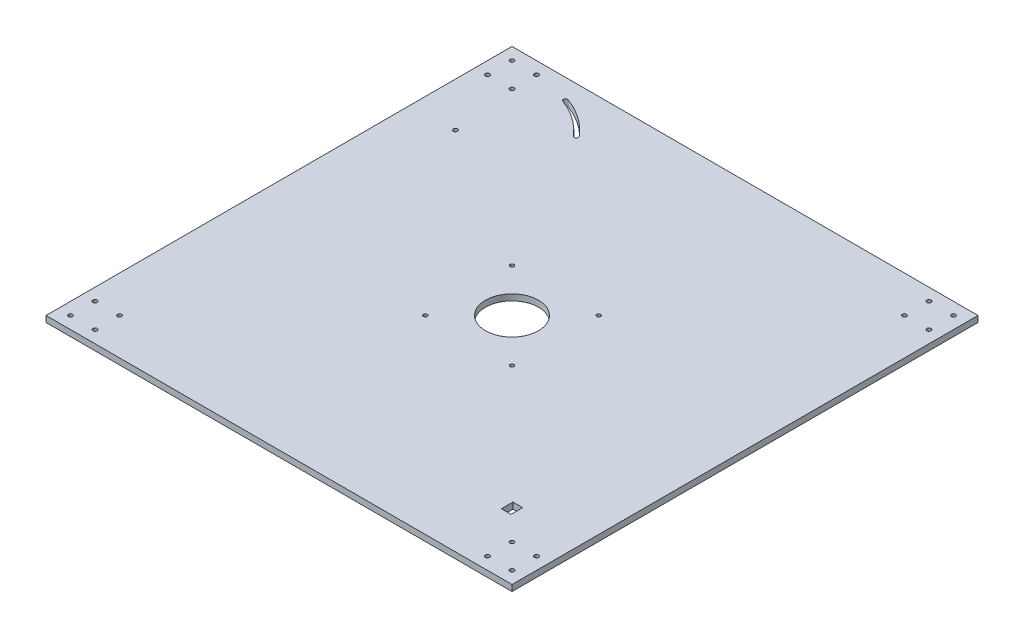
SolidWorks part; units mm, degrees
ref_plane "Front Plane" through (0, 0, 0) normal (0, 0, 1) x (1, 0, 0)
ref_plane "Top Plane" through (0, 0, 0) normal (0, 1, 0) x (1, 0, 0)
ref_plane "Right Plane" through (0, 0, 0) normal (1, 0, 0) x (0, 0, -1)
sketch "Sketch1" plane through (0, 0, 0) normal (0, 1, 0) x (1, 0, 0)
  line L1 (-241.3, -241.3) -> (241.3, -241.3)
  line L2 (-241.3, -241.3) -> (-241.3, 241.3)
  line L3 (-241.3, 241.3) -> (241.3, 241.3)
  line L4 (241.3, -241.3) -> (241.3, 241.3)
  line L5 (-241.3, -241.3) -> (241.3, 241.3) construction
  line L6 (-241.3, 241.3) -> (241.3, -241.3) construction
  point P0 (0, 0)
  dimension "D1" = 482.6
  dimension "D2" = 482.6
extrude "Boss-Extrude1" add sketch "Sketch1" along normal blind 6.35
sketch "Sketch2" plane through (0, 6.35, 0) normal (0, 1, 0) x (1, 0, 0)
  line L1 (-44.8437, -44.8437) -> (44.8437, -44.8437) construction
  line L2 (-44.8437, -44.8437) -> (-44.8437, 44.8437) construction
  line L3 (-44.8437, 44.8437) -> (44.8437, 44.8437) construction
  line L4 (44.8437, -44.8437) -> (44.8437, 44.8437) construction
  line L5 (-44.8437, -44.8437) -> (44.8437, 44.8437) construction
  line L6 (-44.8437, 44.8437) -> (44.8437, -44.8437) construction
  circle A0 centre (-44.8437, 44.8437) radius 1.9844
  circle A1 centre (44.8437, 44.8437) radius 1.9844
  circle A2 centre (-44.8437, -44.8437) radius 1.9844
  circle A3 centre (44.8437, -44.8437) radius 1.9844
  circle A4 centre (0, 0) radius 27.432
  point P0 (0, 0)
  dimension "D3" = 3.9688
  dimension "D4" = 54.864
  dimension "D1" = 89.6874
  dimension "D2" = 89.6874
extrude "Cut-Extrude1" cut sketch "Sketch2" against normal through all and the other way through all
sketch "Sketch3" plane through (0, 6.35, 0) normal (0, 1, 0) x (1, 0, 0)
  line L1 (0, 0) -> (241.3, -241.3) construction
  line L8 (167.8699, -178.8699) -> (177.8699, -178.8699)
  line L9 (167.8699, -178.8699) -> (167.8699, -166.8699)
  line L10 (167.8699, -166.8699) -> (177.8699, -166.8699)
  line L11 (177.8699, -178.8699) -> (177.8699, -166.8699)
  line L12 (167.8699, -178.8699) -> (177.8699, -166.8699) construction
  line L13 (167.8699, -166.8699) -> (177.8699, -178.8699) construction
  point P9 (172.8699, -172.8699)
  dimension "D1" = 244.475
  dimension "D4" = 12
extrude "Cut-Extrude2" cut sketch "Sketch3" against normal through all
sketch "Sketch4" plane through (0, 6.35, 0) normal (0, 1, 0) x (1, 0, 0)
  line L0 (241.3, 241.3) -> (-241.3, 241.3) construction
  line L1 (-215.9, 215.9) -> (215.9, 215.9) construction
  line L2 (-215.9, 215.9) -> (-215.9, -215.9) construction
  line L3 (-215.9, -215.9) -> (215.9, -215.9) construction
  line L4 (215.9, 215.9) -> (215.9, -215.9) construction
  line L5 (-215.9, 215.9) -> (215.9, -215.9) construction
  line L6 (-215.9, -215.9) -> (215.9, 215.9) construction
  line L7 (-241.3, 241.3) -> (-241.3, -241.3) construction
  line L9 (-228.6, 228.6) -> (-203.2, 228.6) construction
  line L10 (-228.6, 228.6) -> (-228.6, 203.2) construction
  line L11 (-228.6, 203.2) -> (-203.2, 203.2) construction
  line L12 (-203.2, 228.6) -> (-203.2, 203.2) construction
  line L13 (-228.6, 228.6) -> (-203.2, 203.2) construction
  line L14 (-228.6, 203.2) -> (-203.2, 228.6) construction
  line L15 (-228.6, -228.6) -> (-203.2, -228.6) construction
  line L16 (-228.6, -228.6) -> (-228.6, -203.2) construction
  line L17 (-228.6, -203.2) -> (-203.2, -203.2) construction
  line L18 (-203.2, -228.6) -> (-203.2, -203.2) construction
  line L19 (-228.6, -228.6) -> (-203.2, -203.2) construction
  line L20 (-228.6, -203.2) -> (-203.2, -228.6) construction
  line L21 (228.6, -228.6) -> (203.2, -228.6) construction
  line L22 (228.6, -228.6) -> (228.6, -203.2) construction
  line L23 (228.6, -203.2) -> (203.2, -203.2) construction
  line L24 (203.2, -228.6) -> (203.2, -203.2) construction
  line L25 (228.6, -228.6) -> (203.2, -203.2) construction
  line L26 (228.6, -203.2) -> (203.2, -228.6) construction
  line L27 (228.6, 228.6) -> (203.2, 228.6) construction
  line L28 (228.6, 228.6) -> (228.6, 203.2) construction
  line L29 (228.6, 203.2) -> (203.2, 203.2) construction
  line L30 (203.2, 228.6) -> (203.2, 203.2) construction
  line L31 (228.6, 228.6) -> (203.2, 203.2) construction
  line L32 (228.6, 203.2) -> (203.2, 228.6) construction
  circle A0 centre (-228.6, 228.6) radius 2.1828
  circle A1 centre (-203.2, 228.6) radius 2.1828
  circle A2 centre (-228.6, 203.2) radius 2.1828
  circle A3 centre (-203.2, 203.2) radius 2.1828
  circle A4 centre (203.2, 228.6) radius 2.1828
  circle A5 centre (203.2, 203.2) radius 2.1828
  circle A6 centre (228.6, 203.2) radius 2.1828
  circle A7 centre (228.6, 228.6) radius 2.1828
  circle A8 centre (203.2, -203.2) radius 2.1828
  circle A9 centre (228.6, -203.2) radius 2.1828
  circle A10 centre (228.6, -228.6) radius 2.1828
  circle A11 centre (203.2, -228.6) radius 2.1828
  circle A12 centre (-228.6, -203.2) radius 2.1828
  circle A13 centre (-203.2, -203.2) radius 2.1828
  circle A14 centre (-203.2, -228.6) radius 2.1828
  circle A15 centre (-228.6, -228.6) radius 2.1828
  point P0 (0, 0)
  dimension "D4" = 4.3656
  dimension "D1" = 25.4
  dimension "D2" = 25.4
  dimension "D3" = 25.4
extrude "Cut-Extrude3" cut sketch "Sketch4" against normal through all
sketch "Sketch5" plane through (0, 6.35, 0) normal (0, 1, 0) x (1, 0, 0)
  line L0 (0, 0) -> (-268.4034, 187.9381) construction
  line L1 (-127.4794, 194.0909) -> (-195.5807, 136.9471) construction
  line L2 (-165.1752, 220.4858) -> (-195.5807, 136.9471) construction
  line L3 (0, 0) -> (0, 241.3) construction
  line L4 (241.3, 241.3) -> (-241.3, 241.3) construction
  circle A0 centre (-195.5807, 136.9471) radius 2.1828
  circle A1 centre (-195.5807, 136.9471) radius 88.9 construction
  arc A2 (-165.1752, 220.4858) -> (-127.4794, 194.0909) centre (-195.5807, 136.9471) cw construction
  arc A3 (-125.8073, 195.494) -> (-164.4286, 222.537) centre (-195.5807, 136.9471) ccw
  arc A4 (-129.1515, 192.6878) -> (-165.9217, 218.4346) centre (-195.5807, 136.9471) ccw
  arc A5 (-129.1515, 192.6878) -> (-125.8073, 195.494) centre (-127.4794, 194.0909) ccw
  arc A6 (-164.4286, 222.537) -> (-165.9217, 218.4346) centre (-165.1752, 220.4858) ccw
  point P7 (-144.5898, 209.7697)
  dimension "D1" = 177.8
  dimension "D2" = 4.3656
  dimension "D3" = 30
  dimension "D6" = 2.1828
  dimension "D4" = 238.76
  dimension "D5" = 75
  dimension "D7" = 55
extrude "Cut-Extrude4" cut sketch "Sketch5" against normal through all
